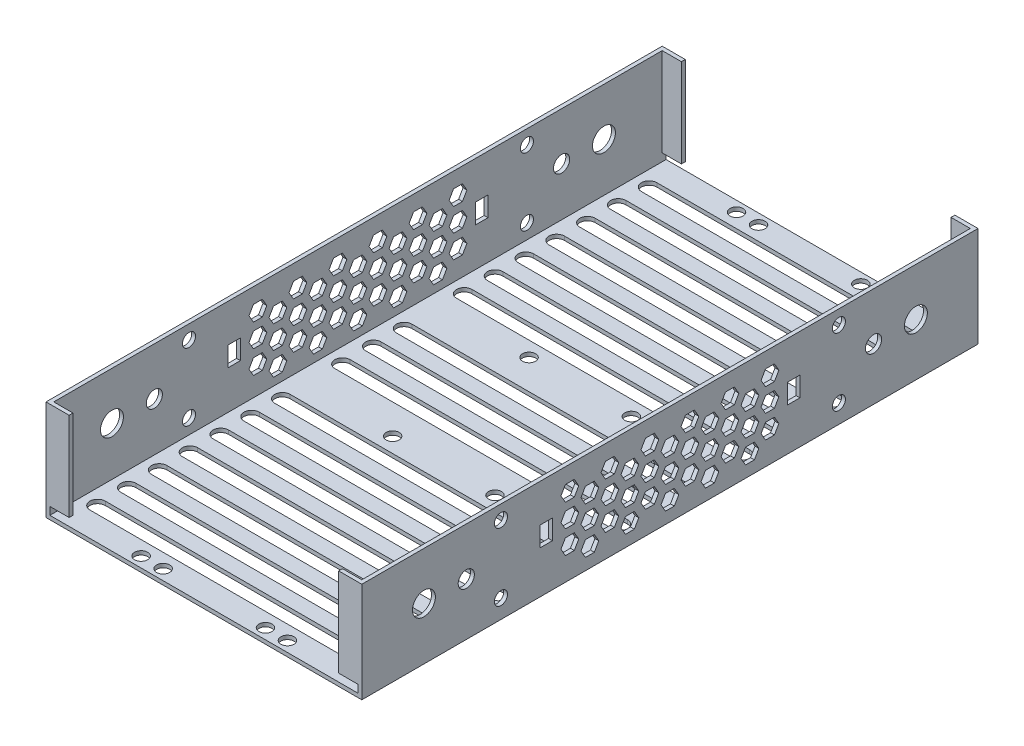
SolidWorks part; units mm, degrees
ref_plane "前视基准面" through (0, 0, 0) normal (0, 0, 1) x (1, 0, 0)
ref_plane "上视基准面" through (0, 0, 0) normal (0, 1, 0) x (1, 0, 0)
ref_plane "右视基准面" through (0, 0, 0) normal (1, 0, 0) x (0, 0, -1)
sketch "草图1" plane through (0, 0, 0) normal (0, 1, 0) x (1, 0, 0)
  line L10 (-40, 80) -> (40, 80)
  line L11 (40, 80) -> (40, -80)
  line L14 (-40, 80) -> (-40, -80)
  line L15 (-40, -80) -> (0, -80)
  line L16 (0, -80) -> (40, -80)
  line L17 (-55, 0) -> (55, 0) construction
  line L18 (0, -55) -> (0, 55) construction
  circle A1 centre (-13.2842, -77.2949) radius 1.7
  circle A2 centre (-13.2842, -17.7064) radius 1.7
  circle A3 centre (-13.2842, 77.2949) radius 1.7
  circle A4 centre (-13.2842, 17.7064) radius 1.7
  circle A5 centre (13.2842, -77.2949) radius 1.7
  circle A6 centre (13.2842, -17.7064) radius 1.7
  circle A7 centre (13.2842, 17.7064) radius 1.7
  circle A8 centre (13.2842, 77.2949) radius 1.7
  circle A10 centre (19, -77.3) radius 1.7
  circle A11 centre (-19, -77.3) radius 1.7
  circle A12 centre (19, 77.3) radius 1.7
  circle A13 centre (-19, 77.3) radius 1.7
  point P6 (0, -80)
extrude "凸台-拉伸1" add sketch "草图1" along normal blind 1 from offset 1
sketch "草图3" plane through (40, 0, 0) normal (1, 0, 0) x (0, 0, -1)
  line L5 (0, 0.55) -> (0, -0.55) construction
  line L8 (-33.759, 12.0422) -> (-30.5136, 12.0422)
  line L9 (-33.759, 12.0422) -> (-33.759, 17.1591)
  line L10 (-33.759, 17.1591) -> (-30.5136, 17.1591)
  line L11 (-30.5136, 12.0422) -> (-30.5136, 17.1591)
  line L14 (80, 1) -> (80, 27)
  line L17 (-80, 27) -> (80, 27)
  line L19 (-80, 27) -> (-80, 1)
  line L20 (-80, 1) -> (80, 1)
  line L25 (33.759, 12.0422) -> (30.5136, 12.0422)
  line L26 (30.5136, 12.0422) -> (30.5136, 17.1591)
  line L27 (33.759, 17.1591) -> (30.5136, 17.1591)
  line L28 (33.759, 12.0422) -> (33.759, 17.1591)
  circle A1 centre (-63.8734, 14.5998) radius 2.98
  circle A3 centre (-52.8734, 14.5998) radius 2.1
  circle A7 centre (52.8734, 14.5998) radius 2.1
  circle A8 centre (63.8734, 14.5998) radius 2.98
  circle A9 centre (-43.8692, 23.3678) radius 1.7
  circle A10 centre (-43.8692, 5.8318) radius 1.7
  circle A11 centre (43.8692, 5.8318) radius 1.7
  circle A12 centre (43.8692, 23.3678) radius 1.7
extrude "凸台-拉伸2" add sketch "草图3" along normal blind 1
sketch "草图11" plane through (-40, 0, -40) normal (1, 0, 0) x (0, 0, -1)
  line L5 (-40, 0.55) -> (-40, -0.55) construction
  line L8 (-73.759, 12.0422) -> (-70.5136, 12.0422)
  line L9 (-73.759, 12.0422) -> (-73.759, 17.1591)
  line L10 (-73.759, 17.1591) -> (-70.5136, 17.1591)
  line L11 (-70.5136, 12.0422) -> (-70.5136, 17.1591)
  line L21 (-70.5136, 12.0422) -> (-70.5136, 17.1591) construction
  line L22 (-73.759, 12.0422) -> (-70.5136, 12.0422) construction
  line L23 (40, 27) -> (40, 1)
  line L24 (40, 1) -> (-120, 1)
  line L25 (-120, 1) -> (-120, 27)
  line L26 (40, 27) -> (-120, 27)
  line L27 (-6.241, 12.0422) -> (-9.4864, 12.0422)
  line L28 (-9.4864, 12.0422) -> (-9.4864, 17.1591)
  line L29 (-6.241, 17.1591) -> (-9.4864, 17.1591)
  line L30 (-6.241, 12.0422) -> (-6.241, 17.1591)
  circle A1 centre (-103.8734, 14.5998) radius 2.98
  circle A3 centre (-92.8734, 14.5998) radius 2.1
  circle A6 centre (12.8734, 14.5998) radius 2.1
  circle A7 centre (23.8734, 14.5998) radius 2.98
  circle A8 centre (-83.8692, 23.3678) radius 1.7
  circle A9 centre (-83.8692, 5.8318) radius 1.7
  circle A10 centre (3.8692, 5.8318) radius 1.7
  circle A11 centre (3.8692, 23.3678) radius 1.7
extrude "凸台-拉伸3" add sketch "草图11" against normal blind 1
sketch "草图12" plane through (0, 0, 0) normal (0, 1, 0) x (1, 0, 0)
  line L0 (36, 63.6059) -> (-36, 63.6059) construction
  line L1 (36, 0) -> (-36, 0) construction
  line L2 (36, 61.6059) -> (-36, 61.6059)
  line L3 (36, 71.6059) -> (-36, 71.6059) construction
  line L4 (36, -2) -> (-36, -2)
  line L5 (36, 65.6059) -> (-36, 65.6059)
  line L6 (36, 69.6059) -> (-36, 69.6059)
  line L7 (36, 73.6059) -> (-36, 73.6059)
  line L8 (36, 55.6059) -> (-36, 55.6059) construction
  line L9 (36, 53.6059) -> (-36, 53.6059)
  line L10 (36, 57.6059) -> (-36, 57.6059)
  line L11 (36, 47.6059) -> (-36, 47.6059) construction
  line L12 (36, 45.6059) -> (-36, 45.6059)
  line L13 (36, 49.6059) -> (-36, 49.6059)
  line L14 (36, 39.6059) -> (-36, 39.6059) construction
  line L15 (36, 37.6059) -> (-36, 37.6059)
  line L16 (36, 41.6059) -> (-36, 41.6059)
  line L17 (36, 31.6059) -> (-36, 31.6059) construction
  line L18 (36, 29.6059) -> (-36, 29.6059)
  line L19 (36, 33.6059) -> (-36, 33.6059)
  line L20 (36, 23.6059) -> (-36, 23.6059) construction
  line L21 (36, 21.6059) -> (-36, 21.6059)
  line L22 (36, 25.6059) -> (-36, 25.6059)
  line L24 (36, -63.6059) -> (-36, -63.6059) construction
  line L25 (36, -61.6059) -> (-36, -61.6059)
  line L26 (36, -65.6059) -> (-36, -65.6059)
  line L27 (36, -71.6059) -> (-36, -71.6059) construction
  line L28 (36, -69.6059) -> (-36, -69.6059)
  line L29 (36, -73.6059) -> (-36, -73.6059)
  line L30 (36, -55.6059) -> (-36, -55.6059) construction
  line L31 (36, -53.6059) -> (-36, -53.6059)
  line L32 (36, -57.6059) -> (-36, -57.6059)
  line L33 (36, -47.6059) -> (-36, -47.6059) construction
  line L34 (36, -45.6059) -> (-36, -45.6059)
  line L35 (36, -49.6059) -> (-36, -49.6059)
  line L36 (36, -39.6059) -> (-36, -39.6059) construction
  line L37 (36, -37.6059) -> (-36, -37.6059)
  line L38 (36, -41.6059) -> (-36, -41.6059)
  line L39 (36, -31.6059) -> (-36, -31.6059) construction
  line L40 (36, -29.6059) -> (-36, -29.6059)
  line L41 (36, -33.6059) -> (-36, -33.6059)
  line L42 (36, -23.6059) -> (-36, -23.6059) construction
  line L43 (36, -21.6059) -> (-36, -21.6059)
  line L44 (36, -25.6059) -> (-36, -25.6059)
  line L45 (36, 2) -> (-36, 2)
  line L46 (36, -8) -> (-36, -8) construction
  line L47 (36, -10) -> (-36, -10)
  line L48 (36, -6) -> (-36, -6)
  line L49 (36, 8) -> (-36, 8) construction
  line L50 (36, 6) -> (-36, 6)
  line L51 (36, 10) -> (-36, 10)
  arc A0 (36, 69.6059) -> (36, 73.6059) centre (36, 71.6059) ccw
  arc A1 (-36, 73.6059) -> (-36, 69.6059) centre (-36, 71.6059) ccw
  arc A2 (36, 61.6059) -> (36, 65.6059) centre (36, 63.6059) ccw
  arc A3 (-36, 65.6059) -> (-36, 61.6059) centre (-36, 63.6059) ccw
  arc A4 (36, 53.6059) -> (36, 57.6059) centre (36, 55.6059) ccw
  arc A5 (-36, 57.6059) -> (-36, 53.6059) centre (-36, 55.6059) ccw
  arc A6 (36, 45.6059) -> (36, 49.6059) centre (36, 47.6059) ccw
  arc A7 (-36, 49.6059) -> (-36, 45.6059) centre (-36, 47.6059) ccw
  arc A8 (36, 37.6059) -> (36, 41.6059) centre (36, 39.6059) ccw
  arc A9 (-36, 41.6059) -> (-36, 37.6059) centre (-36, 39.6059) ccw
  arc A10 (36, 29.6059) -> (36, 33.6059) centre (36, 31.6059) ccw
  arc A11 (-36, 33.6059) -> (-36, 29.6059) centre (-36, 31.6059) ccw
  arc A12 (36, 21.6059) -> (36, 25.6059) centre (36, 23.6059) ccw
  arc A13 (-36, 25.6059) -> (-36, 21.6059) centre (-36, 23.6059) ccw
  arc A14 (36, -61.6059) -> (36, -65.6059) centre (36, -63.6059) cw
  arc A15 (-36, -65.6059) -> (-36, -61.6059) centre (-36, -63.6059) cw
  arc A16 (36, -69.6059) -> (36, -73.6059) centre (36, -71.6059) cw
  arc A17 (-36, -73.6059) -> (-36, -69.6059) centre (-36, -71.6059) cw
  arc A18 (36, -53.6059) -> (36, -57.6059) centre (36, -55.6059) cw
  arc A19 (-36, -57.6059) -> (-36, -53.6059) centre (-36, -55.6059) cw
  arc A20 (36, -45.6059) -> (36, -49.6059) centre (36, -47.6059) cw
  arc A21 (-36, -49.6059) -> (-36, -45.6059) centre (-36, -47.6059) cw
  arc A22 (36, -37.6059) -> (36, -41.6059) centre (36, -39.6059) cw
  arc A23 (-36, -41.6059) -> (-36, -37.6059) centre (-36, -39.6059) cw
  arc A24 (36, -29.6059) -> (36, -33.6059) centre (36, -31.6059) cw
  arc A25 (-36, -33.6059) -> (-36, -29.6059) centre (-36, -31.6059) cw
  arc A26 (36, -21.6059) -> (36, -25.6059) centre (36, -23.6059) cw
  arc A27 (-36, -25.6059) -> (-36, -21.6059) centre (-36, -23.6059) cw
  arc A28 (36, -2) -> (36, 2) centre (36, 0) ccw
  arc A29 (-36, 2) -> (-36, -2) centre (-36, 0) ccw
  arc A30 (36, -10) -> (36, -6) centre (36, -8) ccw
  arc A31 (-36, -6) -> (-36, -10) centre (-36, -8) ccw
  arc A32 (36, 6) -> (36, 10) centre (36, 8) ccw
  arc A33 (-36, 10) -> (-36, 6) centre (-36, 8) ccw
  point P0 (0, 0)
  point P3 (0, 63.6059)
  point P5 (0, 71.6059)
  point P18 (0, 55.6059)
  point P25 (0, 47.6059)
  point P32 (0, 39.6059)
  point P39 (0, 31.6059)
  point P46 (0, 23.6059)
  point P56 (0, -63.6059)
  point P63 (0, -71.6059)
  point P70 (0, -55.6059)
  point P77 (0, -47.6059)
  point P84 (0, -39.6059)
  point P91 (0, -31.6059)
  point P98 (0, -23.6059)
  point P105 (0, -8)
  point P112 (0, 8)
  dimension "D1" = 7
extrude "切除-拉伸1" cut sketch "草图12" along normal blind 10
sketch "草图14" plane through (0, 0, 80) normal (0, 0, 1) x (1, 0, 0)
  line L0 (0, -0.55) -> (0, 0.55) construction
  line L1 (-40, 27) -> (-40, 2) construction
  line L2 (-40, 27) -> (-35, 27)
  line L3 (-35, 27) -> (-35, 4)
  line L4 (-35, 4) -> (-40, 4)
  line L5 (-40, 27) -> (-40, 4)
  line L6 (40, 27) -> (40, 4)
  line L7 (35, 4) -> (40, 4)
  line L8 (35, 27) -> (35, 4)
  line L9 (40, 27) -> (35, 27)
extrude "凸台-拉伸4" add sketch "草图14" against normal blind 1
sketch "草图15" plane through (0, 0, -80) normal (0, 0, -1) x (-1, 0, 0)
  line L0 (-40, 27) -> (-35, 27)
  line L1 (-35, 27) -> (-35, 4)
  line L2 (-35, 4) -> (-40, 4)
  line L3 (-40, 4) -> (-40, 27)
  line L4 (40, 4) -> (35, 4)
  line L5 (35, 4) -> (35, 27)
  line L6 (35, 27) -> (40, 27)
  line L7 (40, 27) -> (40, 4)
extrude "凸台-拉伸5" add sketch "草图15" against normal blind 1
sketch "草图17" plane through (41, 0, 0) normal (1, 0, 0) x (0, 0, -1)
  line L19 (12.7017, 6) -> (11.547, 8)
  line L20 (11.547, 8) -> (9.2376, 8)
  line L21 (9.2376, 8) -> (8.0829, 6)
  line L22 (8.0829, 6) -> (9.2376, 4)
  line L23 (9.2376, 4) -> (11.547, 4)
  line L24 (11.547, 4) -> (12.7017, 6)
  line L25 (17.8979, 9) -> (16.7432, 11)
  line L26 (16.7432, 11) -> (14.4338, 11)
  line L27 (14.4338, 11) -> (13.2791, 9)
  line L28 (13.2791, 9) -> (14.4338, 7)
  line L29 (14.4338, 7) -> (16.7432, 7)
  line L30 (16.7432, 7) -> (17.8979, 9)
  line L31 (23.094, 12) -> (21.9393, 14)
  line L32 (21.9393, 14) -> (19.6299, 14)
  line L33 (19.6299, 14) -> (18.4752, 12)
  line L34 (18.4752, 12) -> (19.6299, 10)
  line L35 (19.6299, 10) -> (21.9393, 10)
  line L36 (21.9393, 10) -> (23.094, 12)
  line L37 (28.2902, 15) -> (27.1355, 17)
  line L38 (27.1355, 17) -> (24.8261, 17)
  line L39 (24.8261, 17) -> (23.6714, 15)
  line L40 (23.6714, 15) -> (24.8261, 13)
  line L41 (24.8261, 13) -> (27.1355, 13)
  line L42 (27.1355, 13) -> (28.2902, 15)
  line L49 (2.3094, 6) -> (1.1547, 8)
  line L50 (1.1547, 8) -> (-1.1547, 8)
  line L51 (-1.1547, 8) -> (-2.3094, 6)
  line L52 (-2.3094, 6) -> (-1.1547, 4)
  line L53 (-1.1547, 4) -> (1.1547, 4)
  line L54 (1.1547, 4) -> (2.3094, 6)
  line L55 (7.5056, 9) -> (6.3509, 11)
  line L56 (6.3509, 11) -> (4.0415, 11)
  line L57 (4.0415, 11) -> (2.8868, 9)
  line L58 (2.8868, 9) -> (4.0415, 7)
  line L59 (4.0415, 7) -> (6.3509, 7)
  line L60 (6.3509, 7) -> (7.5056, 9)
  line L61 (12.7017, 12) -> (11.547, 14)
  line L62 (11.547, 14) -> (9.2376, 14)
  line L63 (9.2376, 14) -> (8.0829, 12)
  line L64 (8.0829, 12) -> (9.2376, 10)
  line L65 (9.2376, 10) -> (11.547, 10)
  line L66 (11.547, 10) -> (12.7017, 12)
  line L67 (17.8979, 15) -> (16.7432, 17)
  line L68 (16.7432, 17) -> (14.4338, 17)
  line L69 (14.4338, 17) -> (13.2791, 15)
  line L70 (13.2791, 15) -> (14.4338, 13)
  line L71 (14.4338, 13) -> (16.7432, 13)
  line L72 (16.7432, 13) -> (17.8979, 15)
  line L73 (23.094, 18) -> (21.9393, 20)
  line L74 (21.9393, 20) -> (19.6299, 20)
  line L75 (19.6299, 20) -> (18.4752, 18)
  line L76 (18.4752, 18) -> (19.6299, 16)
  line L77 (19.6299, 16) -> (21.9393, 16)
  line L78 (21.9393, 16) -> (23.094, 18)
  line L91 (2.3094, 12) -> (1.1547, 14)
  line L92 (1.1547, 14) -> (-1.1547, 14)
  line L93 (-1.1547, 14) -> (-2.3094, 12)
  line L94 (-2.3094, 12) -> (-1.1547, 10)
  line L95 (-1.1547, 10) -> (1.1547, 10)
  line L96 (1.1547, 10) -> (2.3094, 12)
  line L97 (7.5056, 15) -> (6.3509, 17)
  line L98 (6.3509, 17) -> (4.0415, 17)
  line L99 (4.0415, 17) -> (2.8868, 15)
  line L100 (2.8868, 15) -> (4.0415, 13)
  line L101 (4.0415, 13) -> (6.3509, 13)
  line L102 (6.3509, 13) -> (7.5056, 15)
  line L103 (12.7017, 18) -> (11.547, 20)
  line L104 (11.547, 20) -> (9.2376, 20)
  line L105 (9.2376, 20) -> (8.0829, 18)
  line L106 (8.0829, 18) -> (9.2376, 16)
  line L107 (9.2376, 16) -> (11.547, 16)
  line L108 (11.547, 16) -> (12.7017, 18)
  line L109 (17.8979, 21) -> (16.7432, 23)
  line L110 (16.7432, 23) -> (14.4338, 23)
  line L111 (14.4338, 23) -> (13.2791, 21)
  line L112 (13.2791, 21) -> (14.4338, 19)
  line L113 (14.4338, 19) -> (16.7432, 19)
  line L114 (16.7432, 19) -> (17.8979, 21)
  line L133 (2.3094, 18) -> (1.1547, 20)
  line L134 (1.1547, 20) -> (-1.1547, 20)
  line L135 (-1.1547, 20) -> (-2.3094, 18)
  line L136 (-2.3094, 18) -> (-1.1547, 16)
  line L137 (-1.1547, 16) -> (1.1547, 16)
  line L138 (1.1547, 16) -> (2.3094, 18)
  line L139 (7.5056, 21) -> (6.3509, 23)
  line L140 (6.3509, 23) -> (4.0415, 23)
  line L141 (4.0415, 23) -> (2.8868, 21)
  line L142 (2.8868, 21) -> (4.0415, 19)
  line L143 (4.0415, 19) -> (6.3509, 19)
  line L144 (6.3509, 19) -> (7.5056, 21)
  line L191 (7.5056, 27) -> (6.3509, 29) [skipped]
  line L192 (6.3509, 29) -> (4.0415, 29) [skipped]
  line L193 (4.0415, 29) -> (2.8868, 27) [skipped]
  line L194 (2.8868, 27) -> (4.0415, 25) [skipped]
  line L195 (4.0415, 25) -> (6.3509, 25) [skipped]
  line L196 (6.3509, 25) -> (7.5056, 27) [skipped]
  line L197 (2.3094, 24) -> (1.1547, 26) [skipped]
  line L198 (1.1547, 26) -> (-1.1547, 26) [skipped]
  line L199 (-1.1547, 26) -> (-2.3094, 24) [skipped]
  line L200 (-2.3094, 24) -> (-1.1547, 22) [skipped]
  line L201 (-1.1547, 22) -> (1.1547, 22) [skipped]
  line L202 (1.1547, 22) -> (2.3094, 24) [skipped]
  line L203 (12.7017, 24) -> (11.547, 26) [skipped]
  line L204 (11.547, 26) -> (9.2376, 26) [skipped]
  line L205 (9.2376, 26) -> (8.0829, 24) [skipped]
  line L206 (8.0829, 24) -> (9.2376, 22) [skipped]
  line L207 (9.2376, 22) -> (11.547, 22) [skipped]
  line L208 (11.547, 22) -> (12.7017, 24) [skipped]
  line L209 (-8.0829, 18) -> (-9.2376, 20) [skipped]
  line L210 (-9.2376, 20) -> (-11.547, 20) [skipped]
  line L211 (-11.547, 20) -> (-12.7017, 18) [skipped]
  line L212 (-12.7017, 18) -> (-11.547, 16) [skipped]
  line L213 (-11.547, 16) -> (-9.2376, 16) [skipped]
  line L214 (-9.2376, 16) -> (-8.0829, 18) [skipped]
  line L215 (-2.8868, 21) -> (-4.0415, 23) [skipped]
  line L216 (-4.0415, 23) -> (-6.3509, 23) [skipped]
  line L217 (-6.3509, 23) -> (-7.5056, 21) [skipped]
  line L218 (-7.5056, 21) -> (-6.3509, 19) [skipped]
  line L219 (-6.3509, 19) -> (-4.0415, 19) [skipped]
  line L220 (-4.0415, 19) -> (-2.8868, 21) [skipped]
  line L221 (-2.8868, 15) -> (-4.0415, 17) [skipped]
  line L222 (-4.0415, 17) -> (-6.3509, 17) [skipped]
  line L223 (-6.3509, 17) -> (-7.5056, 15) [skipped]
  line L224 (-7.5056, 15) -> (-6.3509, 13) [skipped]
  line L225 (-6.3509, 13) -> (-4.0415, 13) [skipped]
  line L226 (-4.0415, 13) -> (-2.8868, 15) [skipped]
  line L227 (28.2902, 21) -> (27.1355, 23)
  line L228 (27.1355, 23) -> (24.8261, 23)
  line L229 (24.8261, 23) -> (23.6714, 21)
  line L230 (23.6714, 21) -> (24.8261, 19)
  line L231 (24.8261, 19) -> (27.1355, 19)
  line L232 (27.1355, 19) -> (28.2902, 21)
  line L233 (0, 0.55) -> (0, -0.55) construction
  line L234 (-27.1355, 7) -> (-28.2902, 9)
  line L235 (-24.8261, 7) -> (-27.1355, 7)
  line L236 (-23.6714, 9) -> (-24.8261, 7)
  line L237 (-24.8261, 11) -> (-23.6714, 9)
  line L238 (-27.1355, 11) -> (-24.8261, 11)
  line L239 (-28.2902, 9) -> (-27.1355, 11)
  line L240 (-21.9393, 4) -> (-23.094, 6)
  line L241 (-19.6299, 4) -> (-21.9393, 4)
  line L242 (-18.4752, 6) -> (-19.6299, 4)
  line L243 (-19.6299, 8) -> (-18.4752, 6)
  line L244 (-21.9393, 8) -> (-19.6299, 8)
  line L252 (23.094, 6) -> (21.9393, 8)
  line L253 (21.9393, 8) -> (19.6299, 8)
  line L254 (19.6299, 8) -> (18.4752, 6)
  line L255 (18.4752, 6) -> (19.6299, 4)
  line L256 (19.6299, 4) -> (21.9393, 4)
  line L257 (21.9393, 4) -> (23.094, 6)
  line L258 (28.2902, 9) -> (27.1355, 11)
  line L259 (27.1355, 11) -> (24.8261, 11)
  line L260 (24.8261, 11) -> (23.6714, 9)
  line L261 (23.6714, 9) -> (24.8261, 7)
  line L262 (24.8261, 7) -> (27.1355, 7)
  line L263 (27.1355, 7) -> (28.2902, 9)
  line L300 (-23.094, 6) -> (-21.9393, 8)
  line L301 (-27.1355, 19) -> (-28.2902, 21)
  line L302 (-24.8261, 19) -> (-27.1355, 19)
  line L303 (-23.6714, 21) -> (-24.8261, 19)
  line L304 (-24.8261, 23) -> (-23.6714, 21)
  line L305 (-27.1355, 23) -> (-24.8261, 23)
  line L306 (-28.2902, 21) -> (-27.1355, 23)
  line L307 (-6.3509, 19) -> (-7.5056, 21)
  line L308 (-4.0415, 19) -> (-6.3509, 19)
  line L309 (-2.8868, 21) -> (-4.0415, 19)
  line L310 (-4.0415, 23) -> (-2.8868, 21)
  line L311 (-6.3509, 23) -> (-4.0415, 23)
  line L312 (23.094, 0) -> (21.9393, 2) [skipped]
  line L313 (21.9393, 2) -> (19.6299, 2) [skipped]
  line L314 (19.6299, 2) -> (18.4752, 0) [skipped]
  line L315 (18.4752, 0) -> (19.6299, -2) [skipped]
  line L316 (19.6299, -2) -> (21.9393, -2) [skipped]
  line L317 (21.9393, -2) -> (23.094, 0) [skipped]
  line L318 (33.4863, 6) -> (32.3316, 8) [skipped]
  line L319 (32.3316, 8) -> (30.0222, 8) [skipped]
  line L320 (30.0222, 8) -> (28.8675, 6) [skipped]
  line L321 (28.8675, 6) -> (30.0222, 4) [skipped]
  line L322 (30.0222, 4) -> (32.3316, 4) [skipped]
  line L323 (32.3316, 4) -> (33.4863, 6) [skipped]
  line L324 (33.4863, 12) -> (32.3316, 14) [skipped]
  line L325 (32.3316, 14) -> (30.0222, 14) [skipped]
  line L326 (30.0222, 14) -> (28.8675, 12) [skipped]
  line L327 (28.8675, 12) -> (30.0222, 10) [skipped]
  line L328 (30.0222, 10) -> (32.3316, 10) [skipped]
  line L329 (32.3316, 10) -> (33.4863, 12) [skipped]
  line L330 (38.6825, 9) -> (37.5278, 11) [skipped]
  line L331 (37.5278, 11) -> (35.2184, 11) [skipped]
  line L332 (35.2184, 11) -> (34.0637, 9) [skipped]
  line L333 (34.0637, 9) -> (35.2184, 7) [skipped]
  line L334 (35.2184, 7) -> (37.5278, 7) [skipped]
  line L335 (37.5278, 7) -> (38.6825, 9) [skipped]
  line L336 (28.2902, 3) -> (27.1355, 5) [skipped]
  line L337 (27.1355, 5) -> (24.8261, 5) [skipped]
  line L338 (24.8261, 5) -> (23.6714, 3) [skipped]
  line L339 (23.6714, 3) -> (24.8261, 1) [skipped]
  line L340 (24.8261, 1) -> (27.1355, 1) [skipped]
  line L341 (27.1355, 1) -> (28.2902, 3) [skipped]
  line L342 (-7.5056, 21) -> (-6.3509, 23)
  line L439 (17.8979, 3) -> (16.7432, 5) [skipped]
  line L440 (16.7432, 5) -> (14.4338, 5) [skipped]
  line L441 (14.4338, 5) -> (13.2791, 3) [skipped]
  line L442 (13.2791, 3) -> (14.4338, 1) [skipped]
  line L443 (14.4338, 1) -> (16.7432, 1) [skipped]
  line L444 (16.7432, 1) -> (17.8979, 3) [skipped]
  line L445 (-16.7432, 19) -> (-17.8979, 21)
  line L446 (-14.4338, 19) -> (-16.7432, 19)
  line L447 (-13.2791, 21) -> (-14.4338, 19)
  line L448 (-14.4338, 23) -> (-13.2791, 21)
  line L449 (-16.7432, 23) -> (-14.4338, 23)
  line L450 (-17.8979, 21) -> (-16.7432, 23)
  line L451 (-11.547, 16) -> (-12.7017, 18)
  line L452 (-9.2376, 16) -> (-11.547, 16)
  line L453 (-8.0829, 18) -> (-9.2376, 16)
  line L454 (-9.2376, 20) -> (-8.0829, 18)
  line L455 (-11.547, 20) -> (-9.2376, 20)
  line L456 (-12.7017, 18) -> (-11.547, 20)
  line L457 (-6.3509, 13) -> (-7.5056, 15)
  line L458 (-4.0415, 13) -> (-6.3509, 13)
  line L459 (-2.8868, 15) -> (-4.0415, 13)
  line L460 (-4.0415, 17) -> (-2.8868, 15)
  line L461 (-6.3509, 17) -> (-4.0415, 17)
  line L462 (-7.5056, 15) -> (-6.3509, 17)
  line L463 (-21.9393, 16) -> (-23.094, 18)
  line L464 (-19.6299, 16) -> (-21.9393, 16)
  line L465 (-18.4752, 18) -> (-19.6299, 16)
  line L466 (-19.6299, 20) -> (-18.4752, 18)
  line L467 (-21.9393, 20) -> (-19.6299, 20)
  line L468 (-23.094, 18) -> (-21.9393, 20)
  line L469 (-16.7432, 13) -> (-17.8979, 15)
  line L470 (-14.4338, 13) -> (-16.7432, 13)
  line L471 (-13.2791, 15) -> (-14.4338, 13)
  line L472 (-14.4338, 17) -> (-13.2791, 15)
  line L473 (-16.7432, 17) -> (-14.4338, 17)
  line L474 (-17.8979, 15) -> (-16.7432, 17)
  line L475 (-11.547, 10) -> (-12.7017, 12)
  line L476 (-9.2376, 10) -> (-11.547, 10)
  line L477 (-8.0829, 12) -> (-9.2376, 10)
  line L478 (-9.2376, 14) -> (-8.0829, 12)
  line L479 (-11.547, 14) -> (-9.2376, 14)
  line L480 (-12.7017, 12) -> (-11.547, 14)
  line L481 (-6.3509, 7) -> (-7.5056, 9)
  line L482 (-4.0415, 7) -> (-6.3509, 7)
  line L483 (-2.8868, 9) -> (-4.0415, 7)
  line L484 (-4.0415, 11) -> (-2.8868, 9)
  line L485 (-6.3509, 11) -> (-4.0415, 11)
  line L486 (-7.5056, 9) -> (-6.3509, 11)
  line L487 (-27.1355, 13) -> (-28.2902, 15)
  line L488 (-24.8261, 13) -> (-27.1355, 13)
  line L489 (-23.6714, 15) -> (-24.8261, 13)
  line L490 (-24.8261, 17) -> (-23.6714, 15)
  line L491 (-27.1355, 17) -> (-24.8261, 17)
  line L492 (-28.2902, 15) -> (-27.1355, 17)
  line L493 (-21.9393, 10) -> (-23.094, 12)
  line L494 (-19.6299, 10) -> (-21.9393, 10)
  line L495 (-18.4752, 12) -> (-19.6299, 10)
  line L496 (-19.6299, 14) -> (-18.4752, 12)
  line L497 (-21.9393, 14) -> (-19.6299, 14)
  line L498 (-23.094, 12) -> (-21.9393, 14)
  line L499 (-16.7432, 7) -> (-17.8979, 9)
  line L500 (-14.4338, 7) -> (-16.7432, 7)
  line L501 (-13.2791, 9) -> (-14.4338, 7)
  line L502 (-14.4338, 11) -> (-13.2791, 9)
  line L503 (-16.7432, 11) -> (-14.4338, 11)
  line L504 (-17.8979, 9) -> (-16.7432, 11)
  line L505 (-11.547, 4) -> (-12.7017, 6)
  line L506 (-9.2376, 4) -> (-11.547, 4)
  line L507 (-8.0829, 6) -> (-9.2376, 4)
  line L508 (-9.2376, 8) -> (-8.0829, 6)
  line L509 (-11.547, 8) -> (-9.2376, 8)
  line L510 (-12.7017, 6) -> (-11.547, 8)
  circle A1 centre (-5.1962, 21) radius 2 construction
  circle A2 centre (10.3923, 6) radius 2 construction
  circle A3 centre (15.5885, 9) radius 2 construction
  circle A4 centre (20.7846, 12) radius 2 construction
  circle A5 centre (25.9808, 15) radius 2 construction
  circle A7 centre (0, 6) radius 2 construction
  circle A8 centre (5.1962, 9) radius 2 construction
  circle A9 centre (10.3923, 12) radius 2 construction
  circle A10 centre (15.5885, 15) radius 2 construction
  circle A11 centre (20.7846, 18) radius 2 construction
  circle A14 centre (0, 12) radius 2 construction
  circle A15 centre (5.1962, 15) radius 2 construction
  circle A16 centre (10.3923, 18) radius 2 construction
  circle A17 centre (15.5885, 21) radius 2 construction
  circle A21 centre (0, 18) radius 2 construction
  circle A22 centre (5.1962, 21) radius 2 construction
  circle A29 centre (-15.5885, 21) radius 2 construction
  circle A30 centre (-5.1962, 15) radius 2 construction
  circle A31 centre (-10.3923, 18) radius 2 construction
  circle A32 centre (-5.1962, 21) radius 2 construction
  circle A33 centre (-10.3923, 18) radius 2 construction
  circle A34 centre (-5.1962, 15) radius 2 construction
  circle A35 centre (-20.7846, 18) radius 2 construction
  circle A36 centre (0, 24) radius 2 construction
  circle A37 centre (5.1962, 27) radius 2 construction
  circle A38 centre (10.3923, 24) radius 2 construction
  circle A39 centre (-15.5885, 15) radius 2 construction
  circle A40 centre (-10.3923, 12) radius 2 construction
  circle A41 centre (-5.1962, 9) radius 2 construction
  circle A42 centre (-25.9808, 15) radius 2 construction
  circle A43 centre (-20.7846, 12) radius 2 construction
  circle A44 centre (-15.5885, 9) radius 2 construction
  circle A45 centre (-10.3923, 6) radius 2 construction
  dimension "D2" = 5
  dimension "D1" = 3
extrude "切除-拉伸2" cut sketch "草图17" against normal through all
